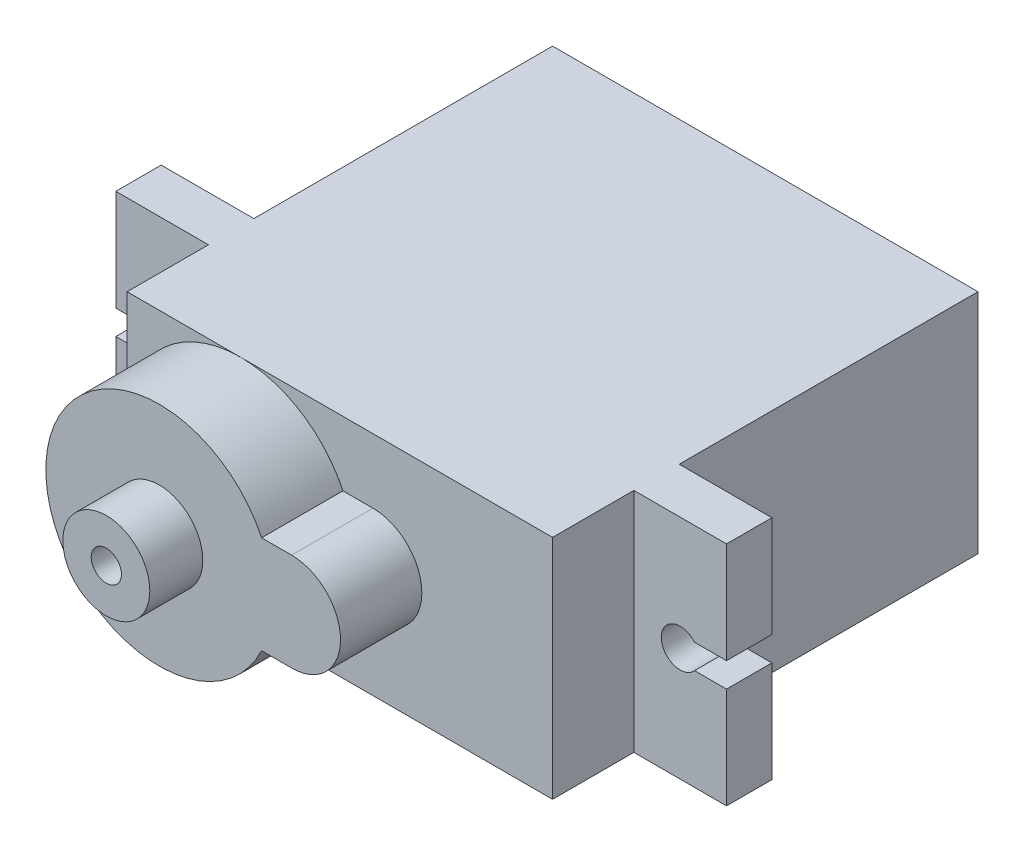
SolidWorks part; units mm, degrees
material "ABS"
ref_plane "Front Plane" through (0, 0, 0) normal (0, 0, 1) x (1, 0, 0)
ref_plane "Top Plane" through (0, 0, 0) normal (0, 1, 0) x (1, 0, 0)
ref_plane "Right Plane" through (0, 0, 0) normal (1, 0, 0) x (0, 0, -1)
sketch "Sketch2" plane through (0, 0, 0) normal (0, 0, 1) x (1, 0, 0)
  line L1 (-15.6538, -2.0258) -> (6.8462, -2.0258)
  line L2 (-15.6538, -2.0258) -> (-15.6538, 9.9742)
  line L3 (-15.6538, 9.9742) -> (6.8462, 9.9742)
  line L4 (6.8462, -2.0258) -> (6.8462, 9.9742)
  dimension "D1" = 12
  dimension "D2" = 22.5
extrude "Boss-Extrude1" add sketch "Sketch2" along normal blind 22.5
sketch "Sketch3" plane through (6.8462, 0, 0) normal (1, 0, 0) x (0, 0, -1)
  line L0 (-22.5, 9.9742) -> (0, 9.9742) construction
  line L1 (-18.2, 9.9742) -> (-15.8, 9.9742)
  line L2 (-18.2, 9.9742) -> (-18.2, -2.0258)
  line L3 (-18.2, -2.0258) -> (-15.8, -2.0258)
  line L4 (-15.8, 9.9742) -> (-15.8, -2.0258)
  line L5 (-22.5, -2.0258) -> (0, -2.0258) construction
  line L6 (-22.5, -2.0258) -> (-22.5, 9.9742) construction
  dimension "D1" = 4.3
  dimension "D2" = 2.4
extrude "Boss-Extrude2" add sketch "Sketch3" along normal blind 4.9 and the other way blind 27.4
sketch "Sketch4" plane through (0, 0, 18.2) normal (0, 0, 1) x (1, 0, 0)
  line L0 (6.8462, 9.9742) -> (11.7462, 9.9742) construction
  line L1 (-20.5538, 9.9742) -> (-15.6538, 9.9742) construction
  line L2 (-20.5538, 9.9742) -> (-20.5538, -2.0258) construction
  circle A0 centre (9.2962, 3.9742) radius 1
  circle A1 centre (-18.1038, 3.9742) radius 1
  point P6 (9.2962, 9.9742)
  point P9 (-18.1038, 9.9742)
  point P12 (-20.5538, 3.9742)
extrude "Cut-Extrude1" cut sketch "Sketch4" against normal up to next
sketch "Sketch5" plane through (0, 0, 22.5) normal (0, 0, 1) x (1, 0, 0)
  circle A0 centre (-9.6538, 3.9742) radius 6
extrude "Boss-Extrude3" add sketch "Sketch5" along normal blind 4.3
sketch "Sketch6" plane through (0, 0, 26.8) normal (0, 0, 1) x (1, 0, 0)
  circle A0 centre (-9.6538, 3.9742) radius 2.3
extrude "Boss-Extrude4" add sketch "Sketch6" along normal blind 2.8
sketch "Sketch7" plane through (0, 0, 29.6) normal (0, 0, 1) x (1, 0, 0)
  circle A0 centre (-9.6538, 3.9742) radius 0.8
extrude "Cut-Extrude2" cut sketch "Sketch7" against normal blind 7
sketch "Sketch8" plane through (0, 0, 18.2) normal (0, 0, 1) x (1, 0, 0)
  line L0 (-20.5538, 9.9742) -> (-20.5538, -2.0258) construction
  line L1 (-22.8879, 4.6242) -> (-18.2197, 4.6242)
  line L2 (-22.8879, 4.6242) -> (-22.8879, 3.3242)
  line L3 (-22.8879, 3.3242) -> (-18.2197, 3.3242)
  line L4 (-18.2197, 4.6242) -> (-18.2197, 3.3242)
  line L5 (-22.8879, 4.6242) -> (-18.2197, 3.3242) construction
  line L6 (-22.8879, 3.3242) -> (-18.2197, 4.6242) construction
  line L7 (11.7462, 9.9742) -> (11.7462, -2.0258) construction
  line L8 (9.6057, 3.3242) -> (13.8866, 3.3242)
  line L9 (9.6057, 3.3242) -> (9.6057, 4.6242)
  line L10 (9.6057, 4.6242) -> (13.8866, 4.6242)
  line L11 (13.8866, 3.3242) -> (13.8866, 4.6242)
  line L12 (9.6057, 3.3242) -> (13.8866, 4.6242) construction
  line L13 (9.6057, 4.6242) -> (13.8866, 3.3242) construction
  point P0 (-20.5538, 3.9742)
  point P7 (11.7462, 3.9742)
  dimension "D1" = 1.3
  dimension "D2" = 1.3
extrude "Cut-Extrude3" cut sketch "Sketch8" against normal up to next
sketch "Sketch9" plane through (0, 0, 22.5) normal (0, 0, 1) x (1, 0, 0)
  line L0 (6.8462, -2.0258) -> (6.8462, 9.9742) construction
  line L1 (-2.6538, 6.5604) -> (-4.2398, 6.5604)
  line L2 (-4.2398, 6.5604) -> (-4.2398, 1.388)
  line L3 (-4.2398, 1.388) -> (-2.6538, 1.388)
  arc A0 (-2.6538, 1.388) -> (-2.6538, 6.5604) centre (-2.6538, 3.9742) ccw
  arc A1 (-9.6538, -2.0258) -> (-9.6538, 9.9742) centre (-9.6538, 3.9742) ccw construction
  point P4 (6.8462, 3.9742)
  point P5 (-3.6538, 3.9742)
  dimension "D1" = 1
extrude "Boss-Extrude6" add sketch "Sketch9" along normal up to surface (4.3 mm away) up to face at (-3.6538, 3.9742, 26.8)
